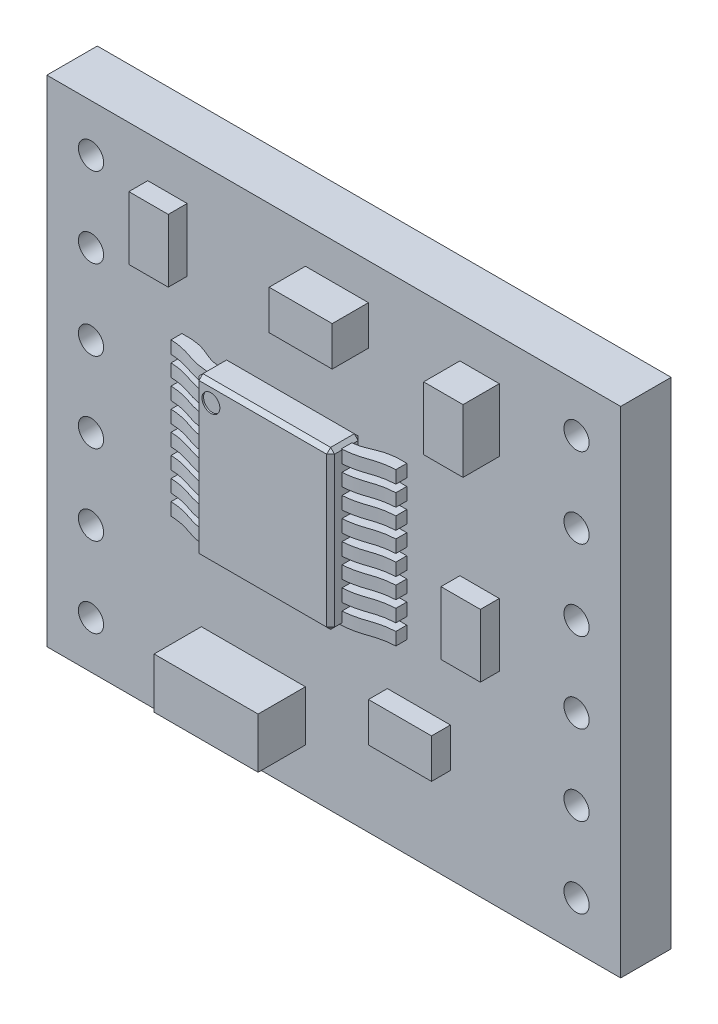
SolidWorks part; units mm, degrees
other "IC (DRV8833)"
other "Board & SMDs"
ref_plane "Plan de face" through (0, 0, 0) normal (0, 0, 1) x (1, 0, 0)
ref_plane "Plan de dessus" through (0, 0, 0) normal (0, 1, 0) x (1, 0, 0)
ref_plane "Plan de droite" through (0, 0, 0) normal (1, 0, 0) x (0, 0, -1)
sketch "Esquisse1" plane through (0, 0, 0) normal (0, 0, 1) x (1, 0, 0)
  line L0 (-9.1, 0) -> (-3.4245, 0) construction
  line L1 (-9.1, -7.85) -> (9.1, -7.85)
  line L2 (-9.1, -7.85) -> (-9.1, 7.85)
  line L3 (-9.1, 7.85) -> (9.1, 7.85)
  line L4 (9.1, -7.85) -> (9.1, 7.85)
  line L5 (-9.1, -7.85) -> (9.1, 7.85) construction
  line L6 (-9.1, 7.85) -> (9.1, -7.85) construction
  line L7 (0, 0) -> (0, 2.4048) construction
  circle A0 centre (-7.7, 1.27) radius 0.4
  circle A1 centre (-7.7, 3.81) radius 0.4
  circle A2 centre (-7.7, 6.35) radius 0.4
  circle A3 centre (-7.7, -6.35) radius 0.4
  circle A4 centre (-7.7, -3.81) radius 0.4
  circle A5 centre (-7.7, -1.27) radius 0.4
  circle A6 centre (7.7, -1.27) radius 0.4
  circle A7 centre (7.7, -3.81) radius 0.4
  circle A8 centre (7.7, -6.35) radius 0.4
  circle A9 centre (7.7, 6.35) radius 0.4
  circle A10 centre (7.7, 3.81) radius 0.4
  circle A11 centre (7.7, 1.27) radius 0.4
  point P0 (0, 0)
  dimension "D3" = 0.8
  dimension "D1" = 18.2
  dimension "D2" = 15.7
  dimension "D4" = 1.4
  dimension "D5" = 1.27
  dimension "D6" = 3
extrude "Boss.-Extru.1" add sketch "Esquisse1" against normal blind 1.6
sketch "Esquisse2" plane through (0, 0, 0) normal (0, 0, 1) x (1, 0, 0)
  line L0 (9.1, -7.85) -> (9.1, 7.85) construction
  line L1 (3.7, -3.6) -> (1.7, -3.6)
  line L2 (3.7, -3.6) -> (3.7, -4.85)
  line L3 (3.7, -4.85) -> (1.7, -4.85)
  line L4 (1.7, -3.6) -> (1.7, -4.85)
  line L5 (-5.9, 6.55) -> (-4.65, 6.55)
  line L6 (-5.9, 6.55) -> (-5.9, 4.55)
  line L7 (-5.9, 4.55) -> (-4.65, 4.55)
  line L8 (-4.65, 6.55) -> (-4.65, 4.55)
  line L9 (4, 0.65) -> (5.25, 0.65)
  line L10 (4, 0.65) -> (4, -1.35)
  line L11 (4, -1.35) -> (5.25, -1.35)
  line L12 (5.25, 0.65) -> (5.25, -1.35)
  line L13 (-9.1, -7.85) -> (9.1, -7.85) construction
  line L14 (9.1, 7.85) -> (-9.1, 7.85) construction
  line L15 (-9.1, 7.85) -> (-9.1, -7.85) construction
  line L17 (5.25, 6.55) -> (4, 6.55)
  line L18 (5.25, 6.55) -> (5.25, 4.55)
  line L19 (5.25, 4.55) -> (4, 4.55)
  line L20 (4, 6.55) -> (4, 4.55)
  line L21 (-0.9, 6.7) -> (1.1, 6.7)
  line L22 (-0.9, 6.7) -> (-0.9, 5.45)
  line L23 (-0.9, 5.45) -> (1.1, 5.45)
  line L24 (1.1, 6.7) -> (1.1, 5.45)
  point P28 (0, 7.85)
  dimension "D1" = 5.4
  dimension "D2" = 2
  dimension "D3" = 1.25
  dimension "D4" = 3
  dimension "D5" = 6.5
  dimension "D6" = 3.85
  dimension "D7" = 1.3
  dimension "D8" = 3.2
  dimension "D9" = 1.3
  dimension "D10" = 3.85
  dimension "D11" = 1.15
  dimension "D12" = 10
extrude "Boss.-Extru.2" add sketch "Esquisse2" along normal blind 0.6 contours L8 L5 L6 L7 | L12 L9 L10 L11 | L1 L4 L3 L2 region at (2.7, -4.225, 0) region at (-5.275, 5.55, 0) region at (4.625, -0.35, 0)
extrude "Boss.-Extru.3" add sketch "Esquisse2<3>" along normal blind 1.15 contours L17 L20 L19 L18 | L24 L21 L22 L23 region at (4.625, 5.55, 0) region at (0.1, 6.075, 0)
sketch "Esquisse2<3>" plane through (0, 0, 0) normal (0, 0, 1) x (1, 0, 0) same geometry as "Esquisse2"
sketch "Esquisse5" plane through (0, 0, 0) normal (0, 0, 1) x (1, 0, 0)
  line L0 (-9.1, 7.85) -> (-9.1, -7.85) construction
  line L1 (-4.2, -4.85) -> (-0.9, -4.85)
  line L2 (-4.2, -4.85) -> (-4.2, -6.45)
  line L3 (-4.2, -6.45) -> (-0.9, -6.45)
  line L4 (-0.9, -4.85) -> (-0.9, -6.45)
  line L5 (-9.1, -7.85) -> (9.1, -7.85) construction
  dimension "D1" = 3.3
  dimension "D2" = 1.6
  dimension "D3" = 4.9
  dimension "D4" = 1.4
extrude "Boss.-Extru.4" add sketch "Esquisse5" along normal blind 1.5
sketch "Esquisse6" plane through (0, 0, 0) normal (0, 0, 1) x (1, 0, 0)
  line L0 (-9.1, 7.85) -> (-9.1, -7.85) construction
  line L1 (-3.4, 3) -> (0.9, 3)
  line L2 (-3.4, 3) -> (-3.4, -2)
  line L3 (-3.4, -2) -> (0.9, -2)
  line L4 (0.9, 3) -> (0.9, -2)
  line L5 (9.1, 7.85) -> (-9.1, 7.85) construction
  dimension "D1" = 5.7
  dimension "D2" = 4.85
  dimension "D3" = 5
  dimension "D4" = 4.3
extrude "Boss.-Extru.5" add sketch "Esquisse6" along normal blind 1 separate body
chamfer "Chanfrein1" distance 0.125 angle 45 12 edges at (-1.25, 3, 1) (0.9, 3, 0.5) (0.9, 0.5, 1) (0.9, -2, 0.5) (-1.25, -2, 1) (-3.4, 3, 0.5) (-3.4, 0.5, 1) (-3.4, -2, 0.5) (-1.25, -2, 0) (0.9, 0.5, 0) (-1.25, 3, 0) (-3.4, 0.5, 0)
sketch "Esquisse7" plane through (0, 0, 1) normal (0, 0, 1) x (1, 0, 0)
  circle A0 centre (-2.8968, 2.4434) radius 0.2833
extrude "Enlèv. mat.-Extru.1" cut sketch "Esquisse7" against normal blind 0.05
sketch "Esquisse8" plane through (0, -2, 0) normal (0, -1, 0) x (1, 0, 0)
  line L0 (-1.25, 0.875) -> (-1.25, 0.4668) construction
  line L1 (0.775, 0.875) -> (-3.275, 0.875) construction
  line L3 (0.775, 0.6463) -> (0.775, 0.3096)
  line L4 (2.3153, 0.3452) -> (2.3153, 0)
  line L5 (-9.1, 0) -> (9.1, 0) construction
  line L6 (-3.275, 0.6463) -> (-3.275, 0.3096)
  line L7 (-4.8153, 0.3452) -> (-4.8153, 0)
  line L8 (0.775, 0.125) -> (0.775, 0.875) construction
  spline S0 degree 3 poles (0.775, 0.6463) (1.5532, 0.6176) (1.6093, 0.3826) (2.3153, 0.3452) knots 0 0 0 0 1 1 1 1
  spline S1 degree 3 poles (0.775, 0.3096) (1.3712, 0.3081) (1.4245, -0.0379) (2.3153, 0) knots 0 0 0 0 1 1 1 1
  spline S2 degree 3 poles (-3.275, 0.6463) (-4.0532, 0.6176) (-4.1093, 0.3826) (-4.8153, 0.3452) knots 0 0 0 0 1 1 1 1
  spline S3 degree 3 poles (-3.275, 0.3096) (-3.8712, 0.3081) (-3.9245, -0.0379) (-4.8153, 0) knots 0 0 0 0 1 1 1 1
  point P16 (0, 0)
  point P17 (0, 0)
extrude "Boss.-Extru.6" add sketch "Esquisse8" against normal blind 0.4 from offset 0.05 offset against normal yes
pattern_linear "Répétition linéaire1" count 8 spacing 0.635 along (0, 1, 0) of "Boss.-Extru.6"
